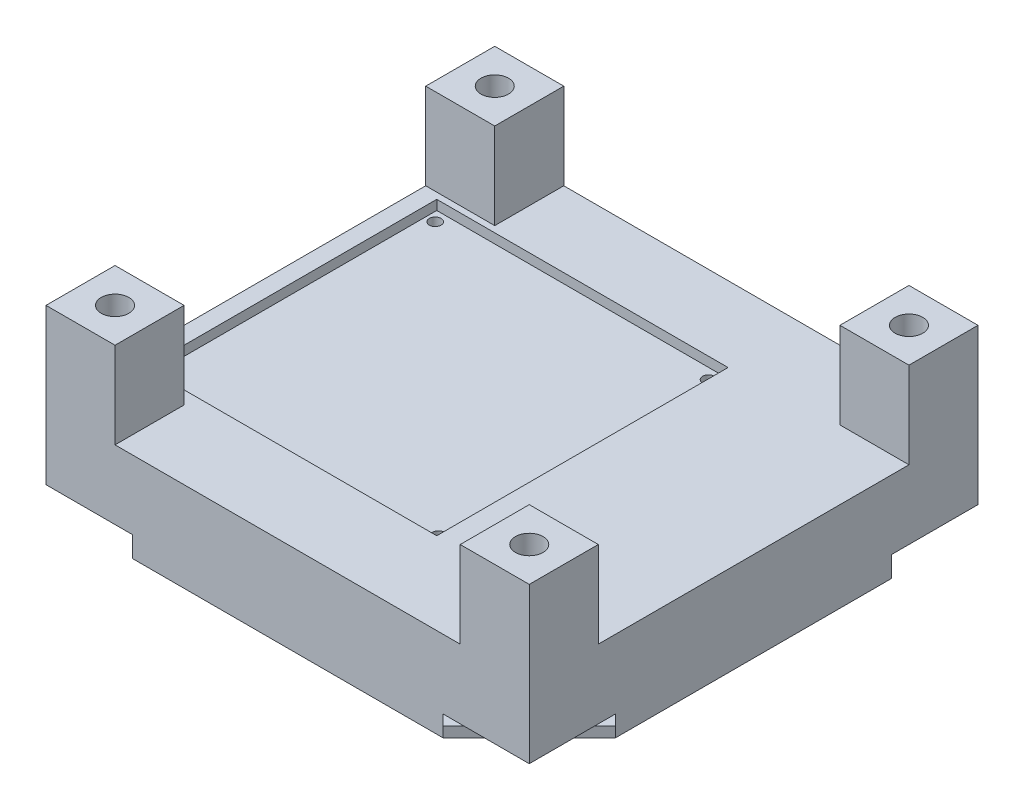
SolidWorks part; units mm, degrees
ref_plane "Front Plane" through (0, 0, 0) normal (0, 0, 1) x (1, 0, 0)
ref_plane "Top Plane" through (0, 0, 0) normal (0, 1, 0) x (1, 0, 0)
ref_plane "Right Plane" through (0, 0, 0) normal (1, 0, 0) x (0, 0, -1)
sketch "Sketch2" plane through (0, 0, 0) normal (0, 1, 0) x (1, 0, 0)
  line L1 (0, 0) -> (177.8, 0)
  line L2 (0, 0) -> (0, -165.1)
  line L3 (0, -165.1) -> (177.8, -165.1)
  line L4 (177.8, 0) -> (177.8, -165.1)
extrude "Boss-Extrude1" add sketch "Sketch2" along normal blind 25.4
ref_axis "Axis1" through (0, 25.4, 82.55) along (1, 0, 0)
ref_axis "Axis2" through (88.9, 25.4, 0) along (0, 0, 1)
ref_plane "Plane1" through (88.9, 0, 0) normal (-1, 0, 0) x (0, 0, 1)
ref_plane "Plane2" through (0, 0, 82.55) normal (0, 0, -1) x (-1, 0, 0)
sketch "Sketch6" plane through (0, 25.4, 0) normal (0, 1, 0) x (1, 0, 0)
  line L1 (0, 0) -> (25.4, 0)
  line L2 (0, 0) -> (0, -25.4)
  line L3 (0, -25.4) -> (25.4, -25.4)
  line L4 (25.4, 0) -> (25.4, -25.4)
extrude "Boss-Extrude2" add sketch "Sketch6" along normal blind 31.75
mirror "Mirror1" about plane through (0, 0, 82.55) normal (0, 0, -1) of "Boss-Extrude2"
mirror "Mirror2" about plane through (88.9, 0, 0) normal (-1, 0, 0) of "Mirror1"
sketch "Sketch9" plane through (0, 25.4, 0) normal (0, 1, 0) x (1, 0, 0)
  line L0 (0, -25.4) -> (25.4, -25.4) construction
  line L4 (6.35, -27.683) -> (113.538, -27.683)
  line L5 (6.35, -27.683) -> (6.35, -134.871)
  line L6 (6.35, -134.871) -> (113.538, -134.871)
  line L7 (113.538, -27.683) -> (113.538, -134.871)
  point P0 (12.7, -25.4)
extrude "Cut-Extrude3" cut sketch "Sketch9" against normal blind 3.556
sketch "Sketch10" plane through (0, 21.844, 0) normal (0, 1, 0) x (1, 0, 0)
  line L0 (6.35, -27.683) -> (9.663, -27.683)
  line L1 (113.538, -27.683) -> (6.35, -27.683) construction
  line L2 (9.663, -27.683) -> (9.663, -31.5739)
  ellipse E0 centre (9.663, -31.5739) end of major axis (10.8613, -29.778) minor radius 2.159
ref_axis "Axis3" through (59.944, 25.4, 27.683) along (0, 0, 1)
ref_axis "Axis4" through (6.35, 25.4, 81.277) along (1, 0, 0)
ref_plane "Plane15" through (0, 0, 81.277) normal (0, 0, 1) x (1, 0, 0)
ref_plane "Plane16" through (59.944, 0, 0) normal (-1, 0, 0) x (0, 0, 1)
extrude "Cut-Extrude4" cut sketch "Sketch10" against normal blind 20.32 contours E0
mirror "Mirror3" about plane through (0, 0, 81.277) normal (0, 0, 1) of "Cut-Extrude4"
mirror "Mirror4" about plane through (59.944, 0, 0) normal (-1, 0, 0) of "Mirror3"
sketch "Sketch14" plane through (0, 57.15, 0) normal (0, 1, 0) x (1, 0, 0)
  circle A0 centre (12.7, -12.7) radius 5.08
extrude "Cut-Extrude5" cut sketch "Sketch14" against normal blind 20.32
mirror "Mirror5" about plane through (88.9, 0, 0) normal (-1, 0, 0) of "Cut-Extrude5"
mirror "Mirror6" about plane through (0, 0, 82.55) normal (0, 0, -1) of "Mirror5"
sketch "Sketch15" plane through (0, 0, 0) normal (0, -1, 0) x (-1, 0, 0)
  line L0 (-146.05, 0) -> (-31.75, 0)
  line L1 (-177.8, 0) -> (0, 0) construction
  line L2 (0, -133.35) -> (0, -31.75)
  line L3 (0, 0) -> (0, -165.1) construction
  line L4 (-31.75, 0) -> (0, -31.75)
  line L5 (13.97, -82.55) -> (-13.97, -82.55) construction
  line L6 (-31.75, -165.1) -> (0, -133.35)
  line L7 (-146.05, -165.1) -> (-31.75, -165.1)
  line L8 (-88.9, -13.97) -> (-88.9, 13.97) construction
  line L9 (-146.05, -165.1) -> (-177.8, -133.35)
  line L10 (-177.8, -133.35) -> (-177.8, -31.75)
  line L11 (-146.05, 0) -> (-177.8, -31.75)
  point P11 (0, -82.55)
  point P16 (-88.9, -165.1)
  point P19 (-88.9, 0)
extrude "Boss-Extrude3" add sketch "Sketch15" along normal blind 7.62
sketch "Sketch16" plane through (15.875, 0, 15.875) normal (-0.7071, 0, -0.7071) x (-0.7071, 0, 0.7071)
  line L0 (22.4506, -7.62) -> (22.4506, 0) construction
  line L1 (-22.4506, 0) -> (22.4506, 0)
  line L2 (-22.4506, 0) -> (-22.4506, -3.81)
  line L3 (-22.4506, -3.81) -> (22.4506, -3.81)
  line L4 (22.4506, 0) -> (22.4506, -3.81)
extrude "Cut-Extrude6" cut sketch "Sketch16" against normal blind 187.96
sketch "Sketch17" plane through (155.575, 0, 155.575) normal (0.7071, 0, 0.7071) x (0.7071, 0, -0.7071)
  line L0 (-13.4704, -7.62) -> (-13.4704, 0) construction
  line L1 (31.4309, 0) -> (-13.4704, 0)
  line L2 (31.4309, 0) -> (31.4309, -3.81)
  line L3 (31.4309, -3.81) -> (-13.4704, -3.81)
  line L4 (-13.4704, 0) -> (-13.4704, -3.81)
extrude "Cut-Extrude7" cut sketch "Sketch17" against normal blind 187.96
sketch "Sketch19" plane through (-66.675, 0, 66.675) normal (-0.7071, 0, 0.7071) x (0.7071, 0, 0.7071)
  line L0 (94.2927, -7.62) -> (94.2927, 0) construction
  line L1 (139.194, 0) -> (94.2927, 0)
  line L2 (139.194, 0) -> (139.194, -3.81)
  line L3 (139.194, -3.81) -> (94.2927, -3.81)
  line L4 (94.2927, 0) -> (94.2927, -3.81)
extrude "Cut-Extrude8" cut sketch "Sketch19" against normal blind 187.96
sketch "Sketch20" plane through (73.025, 0, -73.025) normal (0.7071, 0, -0.7071) x (-0.7071, 0, -0.7071)
  line L0 (-148.1742, -7.62) -> (-148.1742, 0) construction
  line L1 (-103.2729, 0) -> (-148.1742, 0)
  line L2 (-103.2729, 0) -> (-103.2729, -3.81)
  line L3 (-103.2729, -3.81) -> (-148.1742, -3.81)
  line L4 (-148.1742, 0) -> (-148.1742, -3.81)
extrude "Cut-Extrude9" cut sketch "Sketch20" against normal blind 187.96
